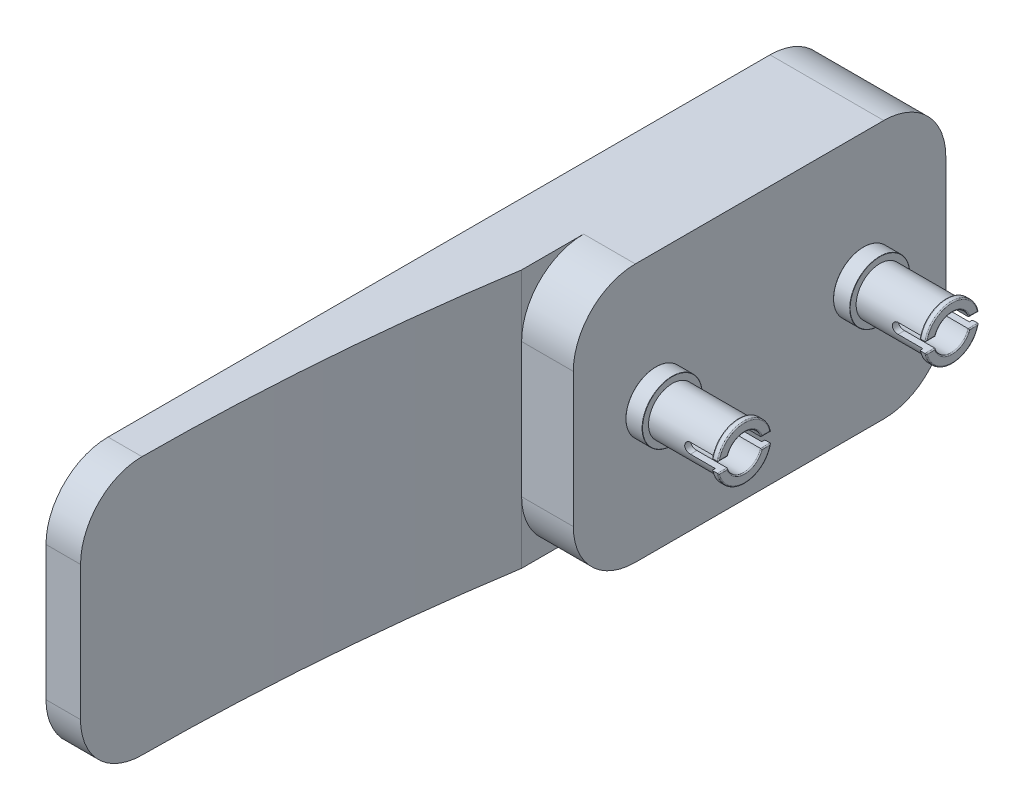
SolidWorks part; units mm, degrees
material "ABS"
ref_plane "Front Plane" through (0, 0, 0) normal (0, 0, 1) x (1, 0, 0)
ref_plane "Top Plane" through (0, 0, 0) normal (0, 1, 0) x (1, 0, 0)
ref_plane "Right Plane" through (0, 0, 0) normal (1, 0, 0) x (0, 0, -1)
sketch "Sketch1" plane through (0, 0, 0) normal (0, 0, 1) x (1, 0, 0)
  line L0 (0, 1.7) -> (0, 2.9)
  line L1 (0, 2.9) -> (-0.8, 2.9)
  line L2 (-0.8, 2.9) -> (-0.8, 2.3)
  line L3 (-0.8, 2.3) -> (-7.2, 2.3)
  line L4 (-7.2, 2.3) -> (-7.2, 2.6)
  line L5 (-7.2, 2.6) -> (-7.8, 2.6)
  line L6 (-7.8, 2.6) -> (-7.8, 1.7)
  line L7 (-7.8, 1.7) -> (0, 1.7)
  line L8 (0, 0) -> (0, 2.9) construction
  line L9 (0, 0) -> (-7.8, 0) construction
  dimension "D1" = 3.4
  dimension "D2" = 4.6
  dimension "D3" = 1.6
  dimension "D4" = 5.8
  dimension "D5" = 15.6
  dimension "D6" = 0.6
  dimension "D7" = 5.2
revolve "Revolve1" add sketch "Sketch1" angle 360 about L9
sketch "Sketch2" plane through (0, 0, 0) normal (0, 0, 1) x (1, 0, 0)
  line L0 (-7.8, 0.5) -> (-4.8, 0.5)
  line L1 (-4.8, -0.5) -> (-7.8, -0.5)
  line L2 (-7.8, -0.5) -> (-7.8, 0.5)
  line L3 (0, 0) -> (0, 3.3644) construction
  line L5 (-7.8, 2.6) -> (-7.8, -2.6) construction
  arc A0 (-4.8, 0.5) -> (-4.8, -0.5) centre (-4.8, 0) cw
  dimension "D1" = 8.6
  dimension "D2" = 1
extrude "Cut-Extrude1" cut sketch "Sketch2" against normal through all both and the other way through all
sketch "Sketch4" plane through (0, 0, 0) normal (0, 1, 0) x (1, 0, 0)
  line L0 (0, 0.5) -> (-2.9, 0.5)
  line L1 (0, -2.9) -> (0, 2.9) construction
  line L2 (-2.9, -0.5) -> (0, -0.5)
  line L3 (0, -0.5) -> (0, 0.5)
  line L4 (0, 0) -> (0, 3.4064) construction
  arc A0 (-2.9, 0.5) -> (-2.9, -0.5) centre (-2.9, 0) ccw
  dimension "D1" = 6.8
  dimension "D2" = 1
extrude "Cut-Extrude2" [suppressed] cut sketch "Sketch4" against normal through all both and the other way through all
ref_plane "Plane1" through (0, 0, 0) normal (0, -0.7071, 0.7071) x (1, 0, 0)
sketch "Sketch3" plane through (0, 0, 0) normal (0, -0.7071, 0.7071) x (1, 0, 0)
  line L0 (-7.2, -2.3) -> (-7.2, 1.2339) construction
  line L1 (-7.2, 0.4) -> (-5.6, 0.4)
  line L2 (-7.2, 0.4) -> (-7.2, -0.4)
  line L3 (-7.2, -0.4) -> (-5.6, -0.4)
  line L4 (-5.6, 0.4) -> (-5.6, -0.4)
  line L5 (-0.8, 2.9) -> (-0.8, -2.9) construction
  line L6 (-0.8, 0.4) -> (-2, 0.4)
  line L7 (-0.8, 0.4) -> (-0.8, -0.4)
  line L8 (-0.8, -0.4) -> (-2, -0.4)
  line L9 (-2, 0.4) -> (-2, -0.4)
  point P6 (-5.6, 0)
  dimension "D1" = 0.8
  dimension "D2" = 1.6
  dimension "D3" = 1.2
extrude "Boss-Extrude1" [suppressed] add sketch "Sketch3" along normal up to surface (0.3041 mm away) from surface
fillet "Fillet1" [suppressed] radius 0.2
fillet "Fillet2" [suppressed] radius 0.025
pattern_circular "CirPattern1" [suppressed] count 4 over 360 of bodies 105
fillet "Fillet3" radius 0.1 8 edges at (-7.8, -2.6, 0) (-7.8, 2.6, 0) (-7.8, 1.7, 0) (-7.8, -1.7, 0) (-7.8, -0.5, 2.0881) (-7.8, 0.5, 2.0881) (-7.8, 0.5, -2.0881) (-7.8, -0.5, -2.0881)
fillet "Fillet4" [suppressed] radius 0.025
fillet "Fillet5" radius 0.025 1 edges at (-0.8, 2.9, 0)
fillet "Fillet6" [suppressed] radius 0.1
fillet "Fillet7" radius 0.1 2 edges at (-7.2, 2.6, 0) (-7.2, -2.6, 0)
mirror "Mirror1" about plane through (0, 1.7, 0) normal (1, 0, 0) of bodies 104 107
ref_plane "Plane2" through (-0.8, 0, 0) normal (-1, 0, 0) x (0, 0, 1)
ref_plane "Plane3" through (0, 0, 10.04) normal (0, 0, 1) x (1, 0, 0)
sketch "Sketch5" plane through (-0.8, 0, 0) normal (-1, 0, 0) x (0, 0, 1)
  line L1 (-7.9721, 12.5) -> (15.8739, 12.5)
  line L2 (-7.9721, 12.5) -> (-7.9721, -12.5)
  line L3 (-7.9721, -12.5) -> (15.8739, -12.5)
  line L4 (15.8739, 12.5) -> (15.8739, -12.5)
  point P4 (-7.9721, 0)
  dimension "D1" = 25
extrude "Boss-Extrude2" add sketch "Sketch5" along normal blind 5
mirror "Mirror3" about plane through (0, 0, 10.04) normal (0, 0, 1) of bodies 109
sketch "Sketch6" plane through (-5.8, 0, 0) normal (-1, 0, 0) x (0, 0, 1)
  line L1 (-7.9721, -12.5) -> (28.0521, -12.5)
  line L2 (-7.9721, -12.5) -> (-7.9721, 12.5)
  line L3 (-7.9721, 12.5) -> (28.0521, 12.5)
  line L4 (28.0521, -12.5) -> (28.0521, 12.5)
extrude "Cut-Extrude3" cut sketch "Sketch6" along normal blind 5
fillet "Fillet8" radius 6 4 edges at (-3.3, 12.5, -7.9721) (-3.3, -12.5, -7.9721) (-3.3, -12.5, 28.0521) (-3.3, 12.5, 28.0521)
sketch "Sketch7" plane through (-5.8, 0, 0) normal (-1, 0, 0) x (0, 0, 1)
  line L4 (22.0521, 12.5) -> (62.0521, 12.5)
  line L5 (68.0521, 6.5) -> (68.0521, -6.5)
  line L6 (62.0521, -12.5) -> (22.0521, -12.5)
  line L7 (28.0521, 6.5) -> (28.0521, -6.5) construction
  line L8 (22.0521, 12.5) -> (-1.9721, 12.5)
  line L9 (-7.9721, 6.5) -> (-7.9721, -6.5)
  line L10 (-1.9721, -12.5) -> (22.0521, -12.5)
  line L11 (28.0521, -6.5) -> (28.0521, 6.5)
  line L12 (22.0521, 12.5) -> (-1.9721, 12.5)
  line L13 (-7.9721, 6.5) -> (-7.9721, -6.5)
  line L14 (-1.9721, -12.5) -> (22.0521, -12.5)
  arc A4 (68.0521, -6.5) -> (62.0521, -12.5) centre (62.0521, -6.5) cw
  arc A5 (62.0521, 12.5) -> (68.0521, 6.5) centre (62.0521, 6.5) cw
  arc A8 (-1.9721, 12.5) -> (-7.9721, 6.5) centre (-1.9721, 6.5) ccw
  arc A9 (-7.9721, -6.5) -> (-1.9721, -12.5) centre (-1.9721, -6.5) ccw
  arc A10 (22.0521, -12.5) -> (28.0521, -6.5) centre (22.0521, -6.5) ccw
  arc A11 (28.0521, 6.5) -> (22.0521, 12.5) centre (22.0521, 6.5) ccw
  arc A12 (-1.9721, 12.5) -> (-7.9721, 6.5) centre (-1.9721, 6.5) ccw
  arc A13 (-7.9721, -6.5) -> (-1.9721, -12.5) centre (-1.9721, -6.5) ccw
  dimension "D2" = 6
  dimension "D3" = 40
  dimension "D1" = 0
extrude "Boss-Extrude3" add sketch "Sketch7" along normal blind 6
sketch "Sketch8" plane through (0, 12.5, 0) normal (0, 1, 0) x (1, 0, 0)
  line L0 (-11.8, -68.0521) -> (-5.8, -68.0521) construction
  line L1 (-8.4575, -68.0521) -> (-5.8, -68.0521)
  line L2 (-5.8, -68.0521) -> (-5.8, -28.0521)
  spline S0 degree 2 poles (-5.8, -28.0521) (-8.9179, -47.9198) (-8.4575, -68.0521) knots 0 0 0 1 1 1
  point P2 (-8.4575, -68.0521)
  point P5 (-7.7756, -44.637)
extrude "Cut-Extrude4" cut sketch "Sketch8" against normal through all
